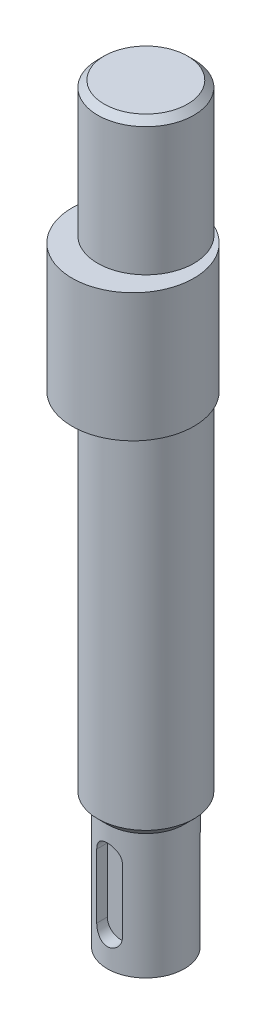
SolidWorks part; units mm, degrees
ref_plane "Front Plane" through (0, 0, 0) normal (1, 0, 0) x (0, 1, 0)
ref_plane "Top Plane" through (0, 0, 0) normal (0, 0, 1) x (0, 1, 0)
ref_plane "Right Plane" through (0, 0, 0) normal (0, 1, 0) x (-1, 0, 0)
sketch "Sketch1" plane through (0, 0, 0) normal (0, 1, 0) x (-1, 0, 0)
  circle A0 centre (0, 0) radius 9.5
  dimension "D1" = 19
extrude "Boss-Extrude1" add sketch "Sketch1" along normal blind 20
sketch "Sketch2" plane through (0, 0, 0) normal (0, -1, 0) x (1, 0, 0)
  circle A0 centre (0, -2) radius 7.5
  circle A1 centre (0, 0) radius 9.5 construction
  dimension "D1" = 15
extrude "Boss-Extrude2" add sketch "Sketch2" along normal blind 58
sketch "Sketch3" plane through (0, -58, 0) normal (0, -1, 0) x (1, 0, 0)
  circle A0 centre (0, -2) radius 6
  dimension "D1" = 12
extrude "Boss-Extrude3" add sketch "Sketch3" along normal blind 18
sketch "Sketch4" plane through (0, 20, 0) normal (0, 1, 0) x (-1, 0, 0)
  circle A0 centre (0, -2) radius 7.5
  circle A1 centre (0, 0) radius 9.5 construction
  dimension "D1" = 15
extrude "Boss-Extrude4" add sketch "Sketch4" along normal blind 21
ref_plane "Plane1" through (0, 0, 4) normal (0, 0, 1) x (0, 1, 0)
sketch "Sketch5" plane through (0, 0, 4) normal (0, 0, 1) x (0, 1, 0)
  line L0 (-71, 0) -> (-61, 0) construction
  line L1 (-71, 2) -> (-61, 2)
  line L2 (-71, -2) -> (-61, -2)
  line L3 (-76, 6) -> (-76, -6) construction
  arc A0 (-71, 2) -> (-71, -2) centre (-71, 0) ccw
  arc A1 (-61, -2) -> (-61, 2) centre (-61, 0) ccw
  point P3 (-66, 0)
  dimension "D1" = 2
  dimension "D2" = 10
  dimension "D3" = 5
extrude "Cut-Extrude1" cut sketch "Sketch5" against normal blind 2
sketch "Sketch6" plane through (0, -76, 0) normal (0, -1, 0) x (1, 0, 0)
  point P0 (0, -2)
hole_wizard "Tap Drill for M4 Tap1" positions "Sketch6" profile "Sketch7" hole size "M4" standard "ISO"
sketch "Sketch7" plane through (0, -76, -2) normal (1, 0, 0) x (0, 0, -1)
  line L0 (0, 0) -> (0, 11.5022)
  line L1 (0, 11.5022) -> (2.5, 10)
  line L2 (2.5, 10) -> (2.5, 0)
  line L5 (2.5, 0) -> (0, 0)
  line L10 (0, 11.5022) -> (-2.5, 10) construction
  line L11 (0, -6.35) -> (0, 107.95) construction
  dimension "Hole Dia." = 5
  dimension "Hole Depth" = 10
  dimension "Drill Angle" = 118
chamfer "Chamfer1" distance 1 angle 45 1 edges at (0, 41, 5.5)
chamfer "Chamfer2" distance 3 angle 45 1 edges at (0, -58, -9.5)
